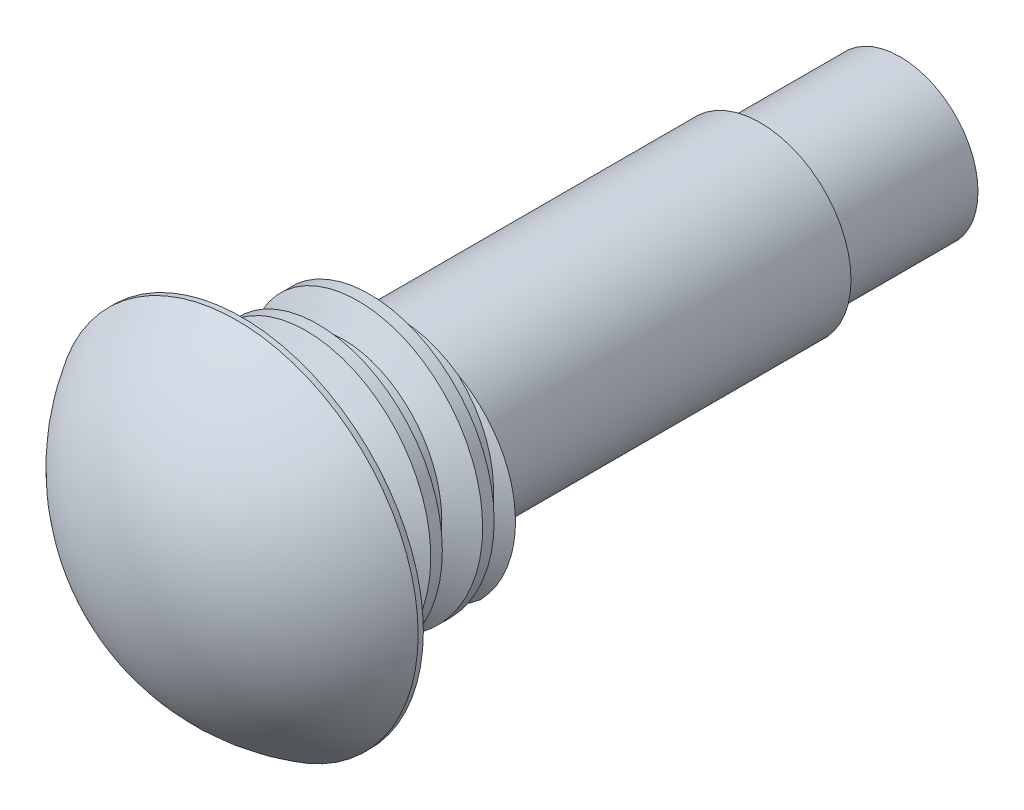
SolidWorks part; units mm, degrees
ref_plane "Front Plane" through (0, 0, 0) normal (0, 0, 1) x (1, 0, 0)
ref_plane "Top Plane" through (0, 0, 0) normal (0, 1, 0) x (1, 0, 0)
ref_plane "Right Plane" through (0, 0, 0) normal (1, 0, 0) x (0, 0, -1)
sketch "Sketch2" plane through (0, 0, 0) normal (0, 0, 1) x (1, 0, 0)
  circle A0 centre (0, 0) radius 3.175
curve "Helix/Spiral1" pitch 1.27 height 3.302 radius 3.175 left hand yes centre (0, 0, 0) axis (0, 0, 1) start towards (0, 1, 0)
sketch "Sketch3" plane through (0, 0, 0) normal (0, 0, 1) x (1, 0, 0)
  circle A0 centre (0, 0) radius 3.175
extrude "Boss-Extrude1" add sketch "Sketch3" along normal blind 3.81 contours A0
sketch "Sketch5" plane through (0, 0, 0) normal (1, 0, 0) x (0, 0, -1)
  line L0 (0.127, 2.54) -> (0.4936, 3.175)
  line L1 (0.4936, 3.175) -> (-0.4936, 3.175)
  line L2 (-0.4936, 3.175) -> (-0.127, 2.54)
  line L3 (-0.127, 2.54) -> (0.127, 2.54)
  line L4 (0, 3.175) -> (0, 2.54) construction
  dimension "D1" = 0.635
  dimension "D2" = 0.254
  dimension "D3" = 60
sweep "Cut-Sweep1" cut profiles "Sketch5" path "Helix/Spiral1" align with end faces yes
sketch "Sketch8" plane through (0, 0, 0) normal (0, 0, 1) x (1, 0, 0)
  circle A0 centre (0, 0) radius 2.2225
extrude "Boss-Extrude3" add sketch "Sketch8" against normal blind 8.89
sketch "Sketch10" plane through (0, 0, -8.89) normal (0, 0, -1) x (-1, 0, 0)
  circle A0 centre (0, 0) radius 1.905
extrude "Boss-Extrude5" add sketch "Sketch10" along normal blind 3.429
sketch "Sketch11" plane through (0, 0, 3.81) normal (0, 0, 1) x (1, 0, 0)
  circle A0 centre (0, 0) radius 4.445
extrude "Boss-Extrude6" add sketch "Sketch11" along normal blind 0.127
dome "Dome1" faces to dome 1 distance 2.54 reverse direction no elliptical dome no face at (4.445, 0, 3.937) parameters "D1"=2.54
